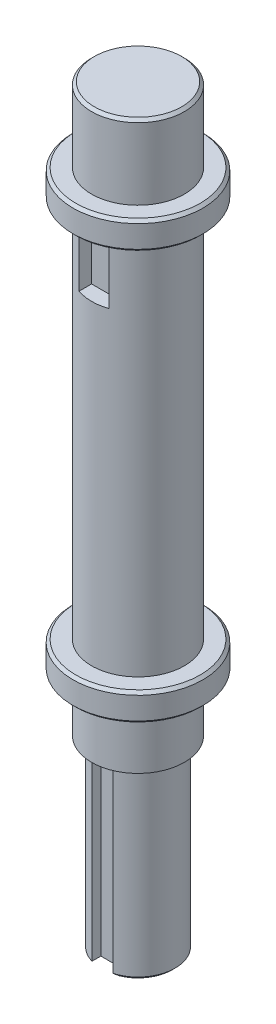
SolidWorks part; units mm, degrees
ref_plane "Front Plane" through (0, 0, 0) normal (0, 0, 1) x (1, 0, 0)
ref_plane "Top Plane" through (0, 0, 0) normal (0, 1, 0) x (1, 0, 0)
ref_plane "Right Plane" through (0, 0, 0) normal (1, 0, 0) x (0, 0, -1)
sketch "Sketch1" plane through (0, 0, 0) normal (0, 0, 1) x (1, 0, 0)
  line L0 (0, 0) -> (5, 0)
  line L1 (5, 0) -> (5, 70)
  line L2 (5, 70) -> (7, 70)
  line L3 (7, 70) -> (7, 73)
  line L4 (7, 73) -> (5, 73)
  line L5 (5, 73) -> (5, 81)
  line L6 (5, 81) -> (0, 81)
  line L7 (0, 81) -> (0, 0)
  dimension "D1" = 5
  dimension "D2" = 7
  dimension "D3" = 3
  dimension "D4" = 70
  dimension "D5" = 8
revolve "Revolve1" add sketch "Sketch1" angle 360 about L7
sketch "Sketch2" plane through (0, 70, 0) normal (0, -1, 0) x (1, 0, 0)
  line L1 (-1.625, 6.625) -> (1.625, 6.625)
  line L2 (-1.625, 6.625) -> (-1.625, 3.375)
  line L3 (-1.625, 3.375) -> (1.625, 3.375)
  line L4 (1.625, 6.625) -> (1.625, 3.375)
  line L5 (-1.625, 6.625) -> (1.625, 3.375) construction
  line L6 (-1.625, 3.375) -> (1.625, 6.625) construction
  circle A0 centre (0, 0) radius 5 construction
  point P0 (0, 5)
  point P7 (0, 0)
  dimension "D1" = 3.25
extrude "Cut-Extrude1" cut sketch "Sketch2" along normal blind 7
ref_axis "Axis1" through (0, 0, 0) along (0, 1, 0)
sketch "Sketch3" plane through (0, 0, 0) normal (0, -1, 0) x (1, 0, 0)
  line L1 (-1.125, 5.125) -> (1.125, 5.125)
  line L2 (-1.125, 5.125) -> (-1.125, 2.875)
  line L3 (-1.125, 2.875) -> (1.125, 2.875)
  line L4 (1.125, 5.125) -> (1.125, 2.875)
  line L5 (-1.125, 5.125) -> (1.125, 2.875) construction
  line L6 (-1.125, 2.875) -> (1.125, 5.125) construction
  circle A0 centre (0, 0) radius 4
  circle A1 centre (0, 0) radius 6.4169
  point P3 (0, 4)
  circle M4 centre (0, 0) radius 5
  dimension "D1" = 8
  dimension "D2" = 2.25
extrude "Cut-Extrude2" cut sketch "Sketch3" against normal blind 20 contours A0 L2 L4 M4 | A1 L1 L4 L2 M4 | L4 A0 L2 L3 | A0 L4 L2 M4 | L4 L1 L2 M4 region at (0, 0, 5.0369) region at (0, 0, 4.4516) region at (-1.2655, 0, 4.3552) region at (0, 0, 3.4119) region at (-6.2354, 0, 0)
ref_plane "Plane1" through (0, 26, 0) normal (0, -1, 0) x (-1, 0, 0)
chamfer "Chamfer1" distance 0.3 angle 45 7 edges at (-5, 81, 0) (-7, 70, 0) (-7, 73, 0) (-1.125, 0, 3.3568) (0, 0, 2.875) (1.125, 0, 3.3568) (0, 0, -4)
sketch "Sketch5" plane through (0, 26, 0) normal (0, -1, 0) x (-1, 0, 0)
  circle A0 centre (0, 0) radius 7 construction
  circle A1 centre (0, 0) radius 7
extrude "Boss-Extrude1" add sketch "Sketch5" against normal blind 3
chamfer "Chamfer2" distance 0.3 angle 45 2 edges at (7, 26, 0) (7, 29, 0)
